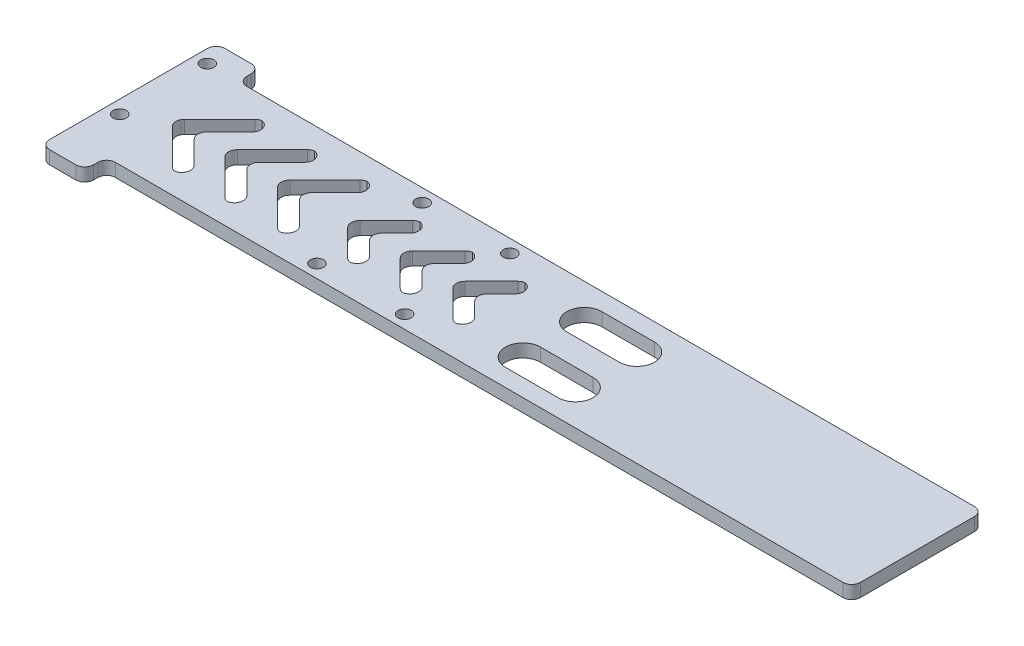
SolidWorks part; units mm, degrees
ref_plane "前视基准面" through (0, 0, 0) normal (0, 0, 1) x (1, 0, 0)
ref_plane "上视基准面" through (0, 0, 0) normal (0, 1, 0) x (1, 0, 0)
ref_plane "右视基准面" through (0, 0, 0) normal (1, 0, 0) x (0, 0, -1)
other "Configuration Table"
sketch "草图1" plane through (0, 0, 0) normal (0, 1, 0) x (1, 0, 0)
  line L0 (55, -12) -> (75, -12) construction
  line L1 (10, -15) -> (180, -15)
  line L3 (10, 15) -> (180, 15)
  line L4 (180, -15) -> (180, 15)
  line L6 (0, 20) -> (10, 20)
  line L7 (10, 20) -> (10, 15)
  line L9 (0, -20) -> (10, -20)
  line L10 (10, -20) -> (10, -15)
  line L11 (0, 0) -> (180, 0) construction
  line L12 (0, 20) -> (0, -20)
  line L13 (3, 15) -> (3, -5) construction
  circle A0 centre (55, -12) radius 1.5
  circle A1 centre (75, -12) radius 1.5
  circle A2 centre (3, 15) radius 1.5
  circle A3 centre (3, -5) radius 1.5
  circle A4 centre (75, 12) radius 1.5
  circle A5 centre (55, 12) radius 1.5
  dimension "D1" = 3
  dimension "D12" = 3
  dimension "D2" = 20
  dimension "D3" = 180
  dimension "D4" = 3
  dimension "D5" = 55
  dimension "D6" = 30
  dimension "D7" = 10
  dimension "D8" = 40
  dimension "D9" = 20
  dimension "D10" = 5
  dimension "D11" = 3
extrude "凸台-拉伸1" add sketch "草图1" along normal blind 3 contours L1 L4 L3 A0 A1 | L7 L6 L3 | L9 L10 L1 region at (88.7974, 0, 0.013)
sketch "草图2" plane through (0, 3, 0) normal (0, 1, 0) x (1, 0, 0)
  line L0 (20, 10) -> (10, 0)
  line L1 (20, 10) -> (25, 10)
  line L2 (25, 10) -> (15, 0)
  line L3 (0, 0) -> (180, 0) construction
  line L4 (180, -15) -> (180, 15) construction
  line L5 (10, 15) -> (180, 15) construction
  line L6 (0, 20) -> (0, -20) construction
  line L7 (20, -10) -> (10, 0)
  line L8 (20, -10) -> (25, -10)
  line L9 (25, -10) -> (15, 0)
  line L10 (32, -10) -> (22, 0)
  line L11 (32, 10) -> (22, 0)
  line L12 (32, 10) -> (37, 10)
  line L13 (37, 10) -> (27, 0)
  line L14 (37, -10) -> (27, 0)
  line L15 (32, -10) -> (37, -10)
  line L16 (44, -10) -> (34, 0)
  line L17 (44, 10) -> (34, 0)
  line L18 (44, 10) -> (49, 10)
  line L19 (49, 10) -> (39, 0)
  line L20 (49, -10) -> (39, 0)
  line L21 (44, -10) -> (49, -10)
  line L22 (50, 0) -> (58, 8)
  line L23 (58, 8) -> (63, 8)
  line L24 (63, 8) -> (55, 0)
  line L25 (55, 12) -> (55, -12) construction
  line L26 (63, -8) -> (55, 0)
  line L27 (58, -8) -> (63, -8)
  line L28 (50, 0) -> (58, -8)
  line L29 (75, -8) -> (67, 0)
  line L30 (75, 8) -> (67, 0)
  line L31 (70, 8) -> (75, 8)
  line L32 (62, 0) -> (70, 8)
  line L33 (62, 0) -> (70, -8)
  line L34 (70, -8) -> (75, -8)
  line L35 (87, -8) -> (79, 0)
  line L36 (87, 8) -> (79, 0)
  line L37 (82, 8) -> (87, 8)
  line L38 (74, 0) -> (82, 8)
  line L39 (74, 0) -> (82, -8)
  line L40 (82, -8) -> (87, -8)
  line L41 (97, 7) -> (109, 7) construction
  line L42 (97, 11) -> (109, 11)
  line L43 (97, 3) -> (109, 3)
  line L44 (97, -7) -> (109, -7) construction
  line L45 (97, -11) -> (109, -11)
  line L46 (97, -3) -> (109, -3)
  arc A0 (97, 11) -> (97, 3) centre (97, 7) ccw
  arc A1 (109, 3) -> (109, 11) centre (109, 7) ccw
  arc A2 (97, -11) -> (97, -3) centre (97, -7) cw
  arc A3 (109, -3) -> (109, -11) centre (109, -7) cw
  point P51 (103, 7)
  point P56 (101.7464, 8)
  point P57 (97.0419, 8)
  point P60 (103, -7)
  point P65 (103.3506, 8)
  point P66 (97.4684, 7)
  dimension "D13" = 4
  dimension "D1" = 5
  dimension "D2" = 5
  dimension "D3" = 10
  dimension "D4" = 45
  dimension "D6" = 7
  dimension "D7" = 5
  dimension "D8" = 45
  dimension "D9" = 7
  dimension "D11" = 7
  dimension "D12" = 3
  dimension "D14" = 12
  dimension "D15" = 10
  dimension "D5" = 3
  dimension "D10" = 3
extrude "切除-拉伸1" cut sketch "草图2" against normal through all
fillet "圆角1" radius 2 44 edges at (10, 1.5, -20) (10, 1.5, -15) (180, 1.5, -15) (180, 1.5, 15) (10, 1.5, 15) (10, 1.5, 20) (0, 1.5, 20) (20, 1.5, -10) (10, 1.5, 0) (20, 1.5, 10) (25, 1.5, 10) (15, 1.5, 0) (25, 1.5, -10) (44, 1.5, -10) (34, 1.5, 0) (44, 1.5, 10) (49, 1.5, 10) (39, 1.5, 0) (49, 1.5, -10) (32, 1.5, -10) (22, 1.5, 0) (32, 1.5, 10) (37, 1.5, 10) (27, 1.5, 0) (37, 1.5, -10) (0, 1.5, -20) (70, 1.5, -8) (75, 1.5, -8) (67, 1.5, 0) (75, 1.5, 8) (70, 1.5, 8) (62, 1.5, 0) (63, 1.5, -8) (55, 1.5, 0) (63, 1.5, 8) (58, 1.5, 8) (50, 1.5, 0) (82, 1.5, -8) (87, 1.5, -8) (79, 1.5, 0) (87, 1.5, 8) (82, 1.5, 8) (74, 1.5, 0) (58, 1.5, -8)
